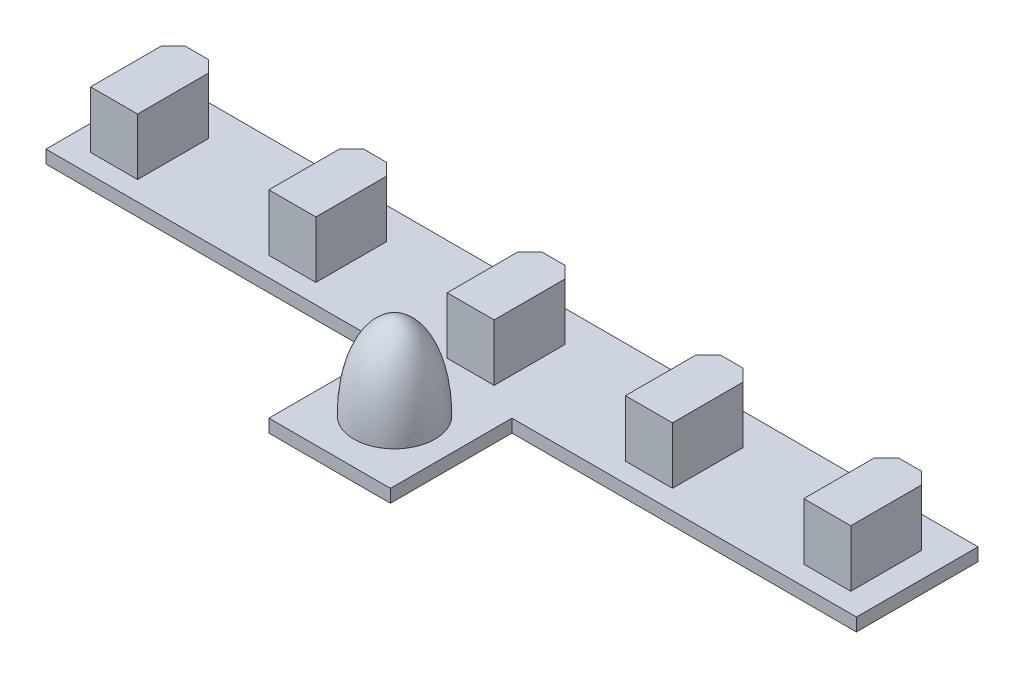
SolidWorks part; units mm, degrees
ref_plane "Front Plane" through (0, 0, 0) normal (0, 0, 1) x (1, 0, 0)
ref_plane "Top Plane" through (0, 0, 0) normal (0, 1, 0) x (1, 0, 0)
ref_plane "Right Plane" through (0, 0, 0) normal (1, 0, 0) x (0, 0, -1)
sketch "Sketch1" plane through (0, 0, 0) normal (0, 1, 0) x (1, 0, 0)
  line L0 (0, -55) -> (0, 55) construction
  line L1 (-7.5, -4.5) -> (7.5, -4.5)
  line L2 (-7.5, -4.5) -> (-7.5, 10.5)
  line L3 (-7.5, 10.5) -> (7.5, 10.5)
  line L4 (7.5, -4.5) -> (7.5, 10.5)
  line L5 (-7.5, -4.5) -> (7.5, 10.5) construction
  line L6 (-7.5, 10.5) -> (7.5, -4.5) construction
  line L7 (-5.28, -2.5) -> (5.28, -2.5)
  line L8 (-5.28, -2.5) -> (-5.28, 2.5)
  line L9 (-5.28, 2.5) -> (5.28, 2.5)
  line L10 (5.28, -2.5) -> (5.28, 2.5)
  line L11 (-5.28, -2.5) -> (5.28, 2.5) construction
  line L12 (-5.28, 2.5) -> (5.28, -2.5) construction
  line L13 (-2.9, 12.9) -> (2.9, 12.9)
  line L14 (-50, 25.5) -> (50, 25.5)
  line L15 (-50, 25.5) -> (-50, 10.5)
  line L16 (-50, 10.5) -> (50, 10.5)
  line L17 (50, 25.5) -> (50, 10.5)
  line L18 (-50, 25.5) -> (50, 10.5) construction
  line L19 (-50, 10.5) -> (50, 25.5) construction
  line L24 (-1.4307, 23.1) -> (1.4307, 23.1)
  line L25 (0, 12.9) -> (0, 23.1) construction
  line L26 (-2.9, 12.9) -> (-2.9, 21.6307)
  line L27 (-2.9, 21.6307) -> (-1.4307, 23.1)
  line L28 (1.4307, 23.1) -> (2.9, 21.6307)
  line L29 (2.9, 21.6307) -> (2.9, 12.9)
  line L30 (24.9, 21.6307) -> (24.9, 12.9)
  line L31 (19.1, 12.9) -> (24.9, 12.9)
  line L32 (19.1, 12.9) -> (19.1, 21.6307)
  line L33 (19.1, 21.6307) -> (20.5693, 23.1)
  line L34 (20.5693, 23.1) -> (23.4307, 23.1)
  line L35 (23.4307, 23.1) -> (24.9, 21.6307)
  line L36 (46.9, 21.6307) -> (46.9, 12.9)
  line L37 (41.1, 12.9) -> (46.9, 12.9)
  line L38 (41.1, 12.9) -> (41.1, 21.6307)
  line L39 (41.1, 21.6307) -> (42.5693, 23.1)
  line L40 (42.5693, 23.1) -> (45.4307, 23.1)
  line L41 (45.4307, 23.1) -> (46.9, 21.6307)
  line L42 (-19.1, 21.6307) -> (-19.1, 12.9)
  line L43 (-24.9, 12.9) -> (-19.1, 12.9)
  line L44 (-24.9, 12.9) -> (-24.9, 21.6307)
  line L45 (-24.9, 21.6307) -> (-23.4307, 23.1)
  line L46 (-23.4307, 23.1) -> (-20.5693, 23.1)
  line L47 (-20.5693, 23.1) -> (-19.1, 21.6307)
  line L48 (-41.1, 21.6307) -> (-41.1, 12.9)
  line L49 (-46.9, 12.9) -> (-41.1, 12.9)
  line L50 (-46.9, 12.9) -> (-46.9, 21.6307)
  line L51 (-46.9, 21.6307) -> (-45.4307, 23.1)
  line L52 (-45.4307, 23.1) -> (-42.5693, 23.1)
  line L53 (-42.5693, 23.1) -> (-41.1, 21.6307)
  point P0 (0, 3)
  point P5 (0, 0)
  point P13 (0, 18)
  point P15 (0, 18)
  point P26 (0, 18)
  dimension "D1" = 15
  dimension "D2" = 15
  dimension "D3" = 10.56
  dimension "D4" = 5
  dimension "D5" = 2
  dimension "D6" = 15
  dimension "D7" = 100
  dimension "D8" = 45
  dimension "D9" = 10.2
  dimension "D10" = 5.8
  dimension "D11" = 3
  dimension "D12" = 3
extrude "Boss-Extrude1" add sketch "Sketch1" along normal blind 1.6 contours L1 L4 L3 L2 L10 L7 L8 L9 | L7 L10 L9 L8 | L17 L14 L15 L16 L3 L28 L29 L13 L26 L27 L24 L34 L35 L30 L31 L32 L33 L40 L41 L36 L37 L38 L39 L46 L47 L42 L43 L44 L45 L52 L53 L48 L49 L50 L51 region at (0, 0, -3.9199) region at (-28.75, 0, -11.5112) region at (0, 0, 0)
extrude "Boss-Extrude2" add sketch "Sketch1<3>" against normal blind 2 contours L7 L10 L9 L8 region at (0, 0, 0)
sketch "Sketch1<3>" plane through (0, 0, 0) normal (0, 1, 0) x (1, 0, 0) same geometry as "Sketch1"
extrude "Boss-Extrude3" add sketch "Sketch1<4>" along normal blind 8.6 contours L35 L34 L33 L32 L31 L30 | L41 L40 L39 L38 L37 L36 | L29 L28 L24 L27 L26 L13 | L47 L46 L45 L44 L43 L42 | L53 L52 L51 L50 L49 L48 region at (0, 0, -17.8254) region at (22, 0, -17.8254) region at (44, 0, -17.8254) region at (-22, 0, -17.8254) region at (-44, 0, -17.8254)
sketch "Sketch1<4>" plane through (0, 0, 0) normal (0, 1, 0) x (1, 0, 0) same geometry as "Sketch1"
sketch "Sketch2" plane through (0, 1.6, 0) normal (0, 1, 0) x (1, 0, 0)
  line L0 (0, -5.83) -> (0, 5.83) construction
  line L1 (-5, -1.5) -> (5, -1.5)
  line L2 (-5, -1.5) -> (-5, 8.5)
  line L3 (-5, 8.5) -> (5, 8.5)
  line L4 (5, -1.5) -> (5, 8.5)
  line L5 (-5, -1.5) -> (5, 8.5) construction
  line L6 (-5, 8.5) -> (5, -1.5) construction
  line L7 (-7.5, -4.5) -> (7.5, -4.5) construction
  point P0 (0, 3.5)
  point P9 (0, 0)
  point P10 (0, 0)
  dimension "D1" = 10
  dimension "D2" = 10
  dimension "D3" = 3
sketch "Sketch3" plane through (0, 0, 0) normal (1, 0, 0) x (0, 0, -1)
  line L0 (-1.5, 1.6) -> (8.5, 1.6)
  line L1 (-1.5, 1.6) -> (8.5, 1.6) construction
  line L2 (-1.5, 1.6) -> (8.5, 1.6) construction
  line L3 (8.5, 1.6) -> (-1.5, 1.6) construction
  line L4 (-1.5, 1.6) -> (-1.5, -3.3247) construction
  line L5 (8.5, 1.6) -> (8.5, -3.3247) construction
  line L6 (-4.5, 1.6) -> (10.5, 1.6) construction
  line L7 (3.5, 12.1) -> (3.5, 1.6)
  line L8 (3.5, 1.6) -> (-1.5, 1.6)
  spline S0 degree 3 poles (-1.5, 1.6) (-1.5, 8.2232) (1, 11.9997) (3.5, 12.1) knots 0 0 0 0 0.5 0.5 0.5 0.5
  dimension "D1" = 10.5
ref_axis "Axis1" through (0, 12.1, -3.5) along (0, -1, 0)
revolve "Revolve2" add sketch "Sketch3" angle 360 about L7 region at (0, 6.0572, -1.3659)
